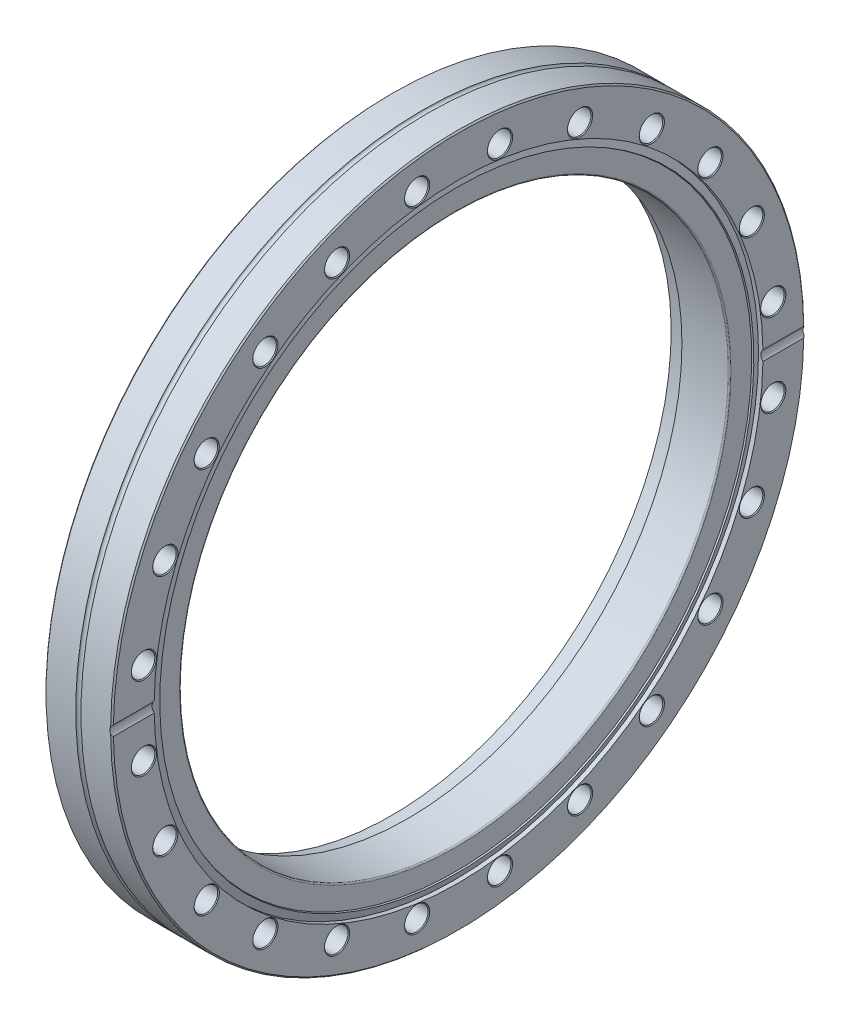
SolidWorks part; units mm, degrees
material "AISI 304"
ref_plane "Спереди" through (0, 0, 0) normal (0, 0, 1) x (1, 0, 0)
ref_plane "Сверху" through (0, 0, 0) normal (0, 1, 0) x (1, 0, 0)
ref_plane "Справа" through (0, 0, 0) normal (1, 0, 0) x (0, 0, -1)
ref_axis "Ось1" through (-110.1507, 0, 0) along (1, 0, 0)
sketch "Эскиз1" plane through (0, 0, 0) normal (0, 0, 1) x (1, 0, 0)
  line L0 (0, 126.6) -> (0, 0) construction
  line L1 (0, 0) -> (-24.95, 0) construction
  line L2 (-24.45, 126.6) -> (-13.6039, 126.6)
  line L3 (-0.35, 126.1) -> (-0.35, 111.2)
  line L4 (-0.35, 111.2) -> (-1.9827, 111.2)
  line L5 (-1.9827, 111.2) -> (-1, 108.5)
  line L6 (-1, 108.5) -> (-1.55, 108.2998)
  line L7 (-1.55, 108.2998) -> (-1.55, 100.7)
  line L8 (-2.05, 100.2) -> (-18.95, 100.2)
  line L9 (-18.95, 100.2) -> (-18.95, 102.25)
  line L10 (-18.95, 102.25) -> (-24.95, 102.25)
  line L11 (-24.95, 102.25) -> (-24.95, 126.1)
  line L12 (-11.6961, 126.6) -> (-0.85, 126.6)
  line L13 (-24.95, 126.1) -> (-24.45, 126.6)
  line L14 (-0.85, 126.6) -> (-0.35, 126.1)
  line L15 (-24.95, 115.95) -> (-0.35, 115.95) construction
  line L16 (-12.65, 126.9) -> (-12.65, 125.9) construction
  arc A0 (-13.6039, 126.6) -> (-11.6961, 126.6) centre (-12.65, 126.9) ccw
  arc A1 (-1.55, 100.7) -> (-2.05, 100.2) centre (-2.05, 100.7) cw
  point P4 (-24.95, 126.6)
  point P5 (-0.35, 126.6)
  point P14 (-24.95, 102.25)
  dimension "D2" = 1
  dimension "D18" = 0.5
  dimension "D1" = 253.2
  dimension "D3" = 12.3
  dimension "D4" = 0.7
  dimension "D5" = 24.6
  dimension "D6" = 204.5
  dimension "D7" = 6
  dimension "D8" = 20
  dimension "D9" = 222.4
  dimension "D10" = 0.65
  dimension "D11" = 217
  dimension "D12" = 1.2
  dimension "D13" = 200.4
  dimension "D14" = 0.5
  dimension "D15" = 45
  dimension "D16" = 0.5
  dimension "D17" = 45
  dimension "D21" = 231.9
  dimension "D23" = 2
revolve "Повернуть2" add sketch "Эскиз1" angle 360 about L1 region at (-12.7112, 113.7769, 0)
sketch "Эскиз7" plane through (-0.35, 0, 0) normal (1, 0, 0) x (0, 0, -1)
  line L0 (0, 0) -> (0, 115.95) construction
  line L1 (15.1345, 114.958) -> (0, 0) construction
  circle A0 centre (0, 0) radius 115.95
  dimension "D1" = 7.5
hole_wizard "Отверстие с зазором M81" positions "Эскиз3" profile "Эскиз2" hole size "M8" standard "DIN" end condition through all
sketch "Эскиз3" plane through (-0.35, 0, 0) normal (1, 0, 0) x (0, 0, -1)
  point P3 (15.1345, 114.958)
sketch "Эскиз2" plane through (-0.35, 114.958, -15.1345) normal (0, 1, 0) x (0, 0, -1)
  line L0 (0, 0) -> (0, 24.6)
  line L1 (0, 24.6) -> (4.6, 24.6)
  line L2 (4.3, 24.3) -> (4.3, 0.3)
  line L3 (4.3, 0.3) -> (4.6, 0)
  line L5 (4.6, 0) -> (0, 0)
  line L6 (-4.3, 0.3) -> (-4.6, 0) construction
  line L7 (4.6, 24.6) -> (4.3, 24.3)
  line L8 (-4.6, 24.6) -> (-4.3, 24.3) construction
  line L11 (0, -6.35) -> (0, 107.95) construction
  dimension "Диаметр сквозного отверстия" = 8.6
  dimension "Глубина сквозного отверстия" = 24.6
  dimension "Диаметр передней зенковки" = 9.2
  dimension "Угол передней зенковки" = 90
  dimension "Диаметр задней зенковки" = 9.2
  dimension "Угол задней зенковки" = 90
pattern_circular "Круговой массив3" count 24 over 360 about axis through (-110.1507, 0, 0) along (1, 0, 0) of "Отверстие с зазором M81"
ref_plane "Плоскость1" through (0, 0, 126.6) normal (0, 0, 1) x (1, 0, 0)
sketch "Эскиз6" plane through (0, 0, 126.6) normal (0, 0, 1) x (1, 0, 0)
  line L0 (3.85, 0) -> (-1.15, 0) construction
  line L1 (0, 0) -> (-24.95, 0) construction
  line L3 (-0.35, 126.1) -> (-0.35, 111.2) construction
  circle A0 centre (1.35, 0) radius 2.5
  dimension "D1" = 5
  dimension "D2" = 0.8
extrude "Вырез-Вытянуть1" cut sketch "Эскиз6" against normal blind 17
pattern_circular "Круговой массив2" count 2 over 360 about axis through (-110.1507, 0, 0) along (1, 0, 0) of "Вырез-Вытянуть1"
